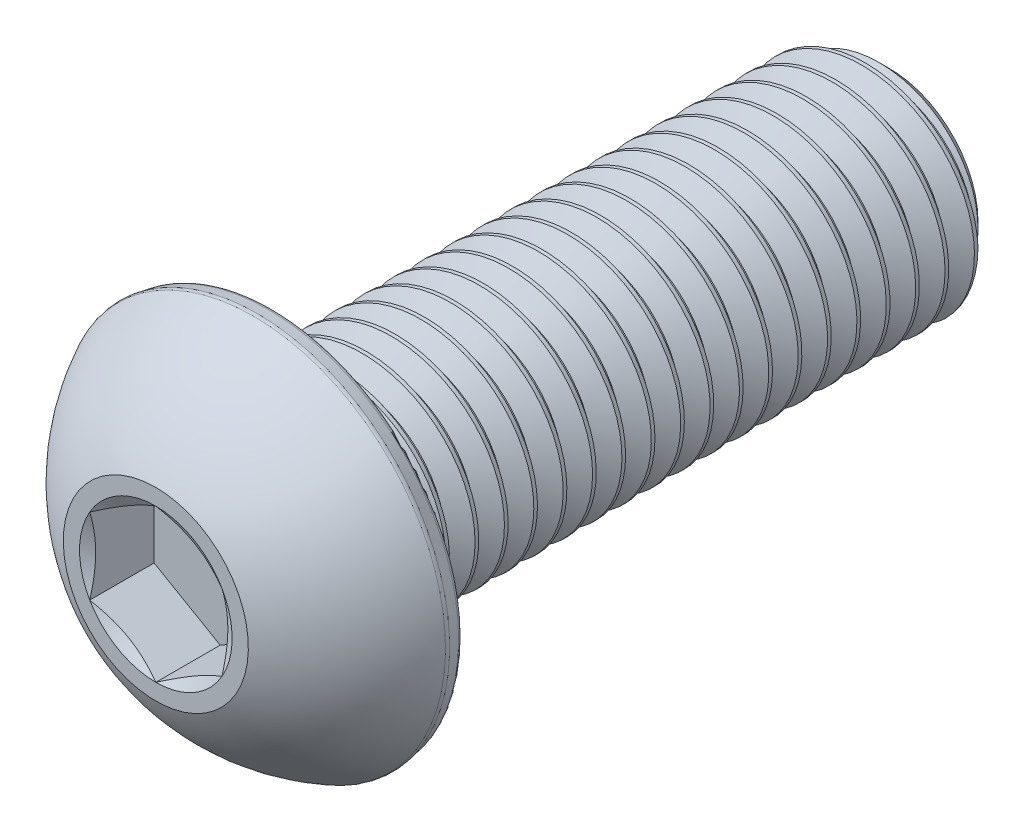
SolidWorks part; units mm, degrees
material "Alloy Steel"
ref_plane "Front Plane" through (0, 0, 0) normal (0, 0, 1) x (1, 0, 0)
ref_plane "Top Plane" through (0, 0, 0) normal (0, 1, 0) x (1, 0, 0)
ref_plane "Right Plane" through (0, 0, 0) normal (1, 0, 0) x (0, 0, -1)
sketch "Sketch1" plane through (0, 0, 0) normal (1, 0, 0) x (0, 0, -1)
  line L0 (-13.2207, 0) -> (13.2207, 0) construction
  line L1 (-13.2207, 0) -> (-13.2207, 6.9469)
  line L2 (-13.2207, 6.9469) -> (-9.0043, 6.9469)
  line L3 (-9.0043, 6.9469) -> (-9.0043, 3.9751)
  line L4 (-9.0043, 3.9751) -> (13.2207, 3.9751)
  line L5 (13.2207, 3.9751) -> (13.2207, 0)
  point P2 (0, 0)
  point P4 (12.1624, 0)
  point P9 (11.6332, 3.9751)
  point P10 (11.6332, -3.9751)
  point P11 (13.2207, -3.9751)
  point P15 (-10.9017, 0)
  dimension "Head Height" = 4.2164
  dimension "Head Diameter" = 13.8938
  dimension "Length" = 22.225
  dimension "Screw Size Decimal Equivalent" = 7.9502
  dimension "Thread Pitch" = 1.0583
  dimension "D1" = 1.5875
  dimension "D2" = 2.319
sketch "Sketch2" plane through (0, 0, 0) normal (0, 0, 1) x (1, 0, 0)
  line L0 (0, 3.9751) -> (0, 0) construction
  line L1 (0, 2.7496) -> (-2.3813, 1.3748)
  line L2 (-2.3813, 1.3748) -> (-2.3812, -1.3748)
  line L3 (-2.3812, -1.3748) -> (0, -2.7496)
  line L4 (0, -2.7496) -> (2.3813, -1.3748)
  line L5 (2.3813, -1.3748) -> (2.3813, 1.3748)
  line L6 (2.3813, 1.3748) -> (0, 2.7496)
  circle A0 centre (0, 0) radius 2.3813 construction
  circle A1 centre (0, 0) radius 3.3337
  point P10 (0, 3.3337)
  dimension "D1" = 6.6675
  dimension "Drive Size" = 4.7625
sketch "Sketch3" plane through (0, 0, 0) normal (1, 0, 0) x (0, 0, -1)
  line L0 (-13.2207, 0) -> (-13.2207, 3.3337)
  line L1 (-13.2207, 0) -> (-13.2207, 6.9469) construction
  line L2 (-13.2207, 6.9469) -> (-9.0043, 6.9469) construction
  line L3 (-9.6368, 6.9469) -> (-9.0043, 6.8354)
  line L4 (-9.0043, 6.9469) -> (-9.0043, 3.9751) construction
  line L5 (-9.0043, 6.8354) -> (-9.0043, 3.9751)
  line L6 (-13.2207, 0) -> (13.2207, 0) construction
  line L7 (-13.2207, 0) -> (13.2207, 0)
  line L8 (13.2207, 0) -> (13.2207, 3.1813)
  line L9 (13.2207, 3.9751) -> (13.2207, 0) construction
  line L10 (13.2207, 3.1813) -> (12.4269, 3.9751)
  line L11 (-9.0043, 3.9751) -> (13.2207, 3.9751) construction
  line L12 (12.4269, 3.9751) -> (-9.0043, 3.9751)
  arc A0 (-13.2207, 3.3337) -> (-9.6368, 6.9469) centre (-6.2465, 0) cw
  dimension "D1" = 0.6325
  dimension "D2" = 10
  dimension "D3" = 45
  dimension "D4" = 0.7938
revolve "Revolve1" add sketch "Sketch3" angle 360 about L7
sketch "Sketch4" plane through (0, 0, 13.2207) normal (0, 0, 1) x (1, 0, 0)
  line L0 (-2.3812, -1.3748) -> (0, -2.7496) construction
  line L1 (-2.3813, 1.3748) -> (-2.3812, -1.3748) construction
  line L2 (0, 2.7496) -> (-2.3813, 1.3748) construction
  line L3 (2.3813, 1.3748) -> (0, 2.7496) construction
  line L4 (2.3813, -1.3748) -> (2.3813, 1.3748) construction
  line L5 (0, -2.7496) -> (2.3813, -1.3748) construction
  line L6 (-2.3812, -1.3748) -> (0, -2.7496)
  line L7 (-2.3813, 1.3748) -> (-2.3812, -1.3748)
  line L8 (0, 2.7496) -> (-2.3813, 1.3748)
  line L9 (2.3813, 1.3748) -> (0, 2.7496)
  line L10 (2.3813, -1.3748) -> (2.3813, 1.3748)
  line L11 (0, -2.7496) -> (2.3813, -1.3748)
extrude "Cut-Extrude1" cut sketch "Sketch4" against normal up to vertex (2.319 mm away) up to point (0, 0, 10.9017)
sketch "Sketch5" plane through (0, 0, 13.2207) normal (0, 0, 1) x (1, 0, 0)
  circle A0 centre (0, 0) radius 2.7496
extrude "Cut-Extrude2" cut sketch "Sketch5" against normal up to vertex (2.319 mm away) draft 60 up to point (0, 0, 10.9017)
fillet "Fillet1" radius 0.2108 2 edges at (6.9469, 0, 9.6368) (6.8354, 0, 9.0043)
split "Split1" bodies to split 106 resulting bodies 107 108 split by face at (6.6585, 0, 9.0043)
sketch "Sketch6" plane through (0, 0, -13.2207) normal (0, 0, -1) x (-1, 0, 0)
  circle A0 centre (0, 0) radius 3.9751 construction
  circle A1 centre (0, 0) radius 3.9751
curve "Helix/Spiral1" pitch 1.0583 height 23.2833 radius 3.9751 centre (0, 0, -13.2207) axis (0, 0, 1) start towards (0, 1, 0)
sketch "Sketch7" plane through (0, 0, 0) normal (1, 0, 0) x (0, 0, -1)
  line L0 (13.1546, 4.0897) -> (13.6837, 3.1731) construction
  line L1 (13.6837, 3.1731) -> (14.2129, 4.0897) construction
  line L2 (14.2129, 4.0897) -> (13.1546, 4.0897) construction
  line L3 (13.1876, 4.0324) -> (14.1798, 4.0324)
  line L4 (14.1798, 4.0324) -> (13.7499, 3.2877)
  line L5 (13.7499, 3.2877) -> (13.6176, 3.2877)
  line L6 (13.6176, 3.2877) -> (13.1876, 4.0324)
  line L7 (13.6837, 3.2877) -> (13.6837, 3.1731) construction
  line L8 (13.2207, 3.9751) -> (14.1467, 3.9751) construction
  line L9 (13.6837, 4.0897) -> (13.6837, 3.9751) construction
  point P12 (13.6837, 4.0324)
  dimension "D1" = 1.0583
  dimension "D2" = 0.1323
sweep "Cut-Sweep1" cut profiles "Sketch7" path "Helix/Spiral1" align with end faces yes
sketch "Sketch8" plane through (0, 0, 9.0043) normal (0, 0, -1) x (-1, 0, 0)
  circle A0 centre (0, 0) radius 4.0897
extrude "Boss-Extrude1" add sketch "Sketch8" along normal up to vertex (20.6375 mm away) draft 45 up to point (0, 3.9751, -11.6332)
equation "\"D1@Sketch1\"=\"Thread Pitch@Sketch1\"*1.5"
equation "\"D2@Sketch1\"=0.55*\"Head Height@Sketch1\""
equation "\"D1@Sketch2\"=\"Drive Size@Sketch2\"*1.4"
equation "\"D1@Sketch3\"=0.15*\"Head Height@Sketch1\""
equation "\"D4@Sketch3\"=0.75*\"Thread Pitch@Sketch1\""
equation "\"D1@Fillet1\"=.05*\"Head Height@Sketch1\""
equation "\"D4@Helix/Spiral1\"=\"Thread Pitch@Sketch1\""
equation "\"D3@Helix/Spiral1\"=\"Length@Sketch1\"+\"Thread Pitch@Sketch1\""
equation "\"D2@Sketch7\"=\"D1@Sketch7\"/8"
equation "\"D1@Sketch7\"=\"Thread Pitch@Sketch1\""
